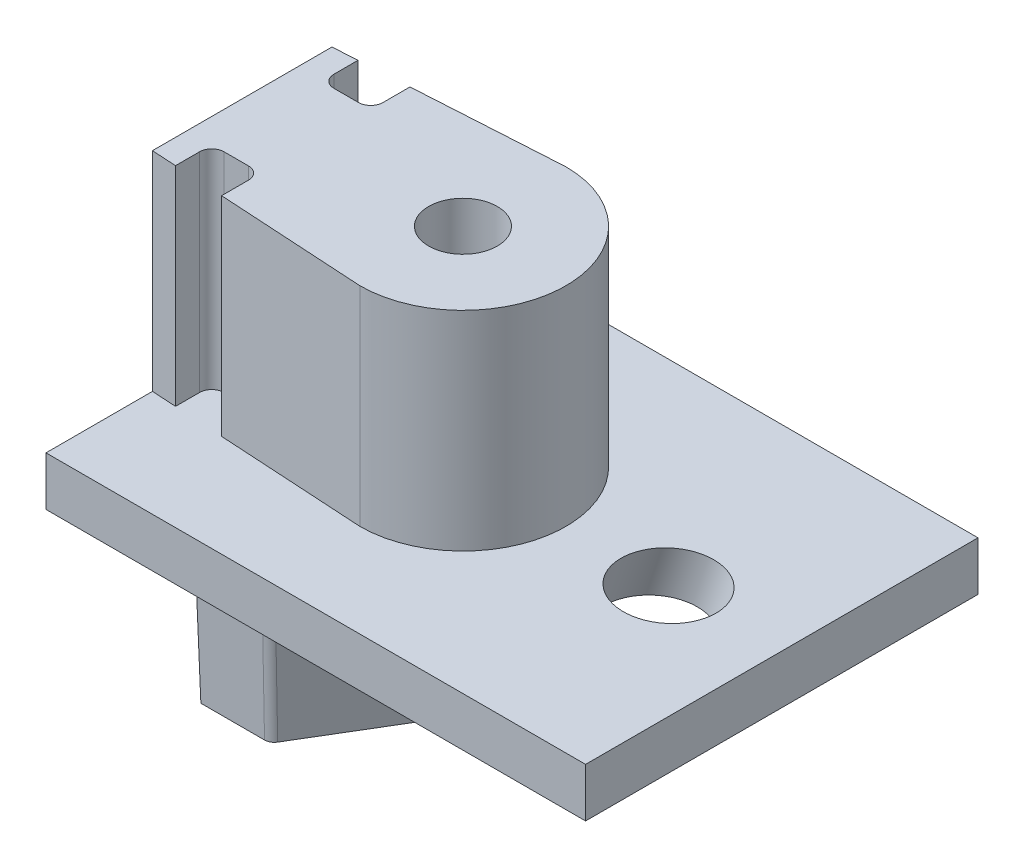
SolidWorks part; units mm, degrees
ref_plane "Front Plane" through (0, 0, 0) normal (0, 0, 1) x (1, 0, 0)
ref_plane "Top Plane" through (0, 0, 0) normal (0, 1, 0) x (1, 0, 0)
ref_plane "Right Plane" through (0, 0, 0) normal (1, 0, 0) x (0, 0, -1)
sketch "Sketch3" plane through (0, 0, 0) normal (0, 1, 0) x (1, 0, 0)
  line L0 (-5, 0.75) -> (0, 1.05) construction
  line L3 (0, -1.05) -> (-5, -0.75) construction
  line L4 (-2.5, 0.9) -> (-2, 0.93)
  line L6 (-4.25, 0) -> (-5.75, 0) construction
  line L7 (-2, 0.93) -> (-2, 0.56)
  line L8 (-2.5, 0.9) -> (-5, 0.9) construction
  line L9 (-2.5, 0.9) -> (-2.5, -0.9)
  line L10 (-2.5, -0.9) -> (-5, -0.9) construction
  line L11 (-5, 0.9) -> (-5, -0.9) construction
  line L12 (-2, 0.96) -> (-1.5, 0.96) construction
  line L13 (-2, 0.96) -> (-2, 0.56) construction
  line L14 (-2, 0.56) -> (-1.5, 0.56)
  line L15 (-1.5, 0.96) -> (-1.5, 0.56)
  line L16 (-1.5, -0.56) -> (-2, -0.56)
  line L17 (-1.5, -0.56) -> (-1.5, -0.96)
  line L18 (-1.5, -0.96) -> (-2, -0.96) construction
  line L19 (-2, -0.56) -> (-2, -0.96) construction
  line L21 (-2.5, -0.9) -> (-2, -0.93)
  line L22 (-2, -0.93) -> (-2, -0.56)
  line L23 (-1.5, 0.96) -> (0, 1.05)
  line L24 (0, -1.05) -> (-1.5, -0.96)
  circle A2 centre (0, 0) radius 0.6 construction
  circle A3 centre (0, 0) radius 0.4 construction
  circle A4 centre (-5, 0) radius 0.35 construction
  circle A5 centre (0, 0) radius 1.05 construction
  circle A6 centre (-5, 0) radius 0.75 construction
  arc A7 (-5, 0.9) -> (-5, -0.9) centre (-5, 0) ccw construction
  arc A8 (0, 1.05) -> (0, -1.05) centre (0, 0) cw
  point P4 (-2, -0.93)
  point P15 (-5, 0)
  point P16 (-2, 0.93)
  point P22 (-5, 0)
  dimension "D2" = 1.2
  dimension "D3" = 0.8
  dimension "D4" = 0.7
  dimension "D6" = 5
  dimension "D1" = 1.5
  dimension "D5" = 2.1
  dimension "D7" = 0.4
  dimension "D9" = 2.5
  dimension "D10" = 1.8
  dimension "D11" = 2.5
  dimension "D12" = 0.5
  dimension "D14" = 1.5
extrude "Boss-Extrude1" add sketch "Sketch3" along normal blind 2.125 contours L21 L22 L16 L17 L24 A8 L23 L15 L14 L7 L4 L9
sketch "Sketch4" plane through (0, 2.125, 0) normal (0, 1, 0) x (1, 0, 0)
  circle A0 centre (0, 0) radius 0.35
  point P9 (0, 0)
  dimension "D1" = 0.7
extrude "Through Holes" cut sketch "Sketch4" against normal through all
fillet "Fillet1" radius 0.125 4 edges at (-2, 1.0625, 0.56) (-1.5, 1.0625, 0.56) (-1.5, 1.0625, -0.56) (-2, 1.0625, -0.56)
sketch "Sketch5" plane through (0, 0, 0) normal (0, 1, 0) x (1, 0, 0)
  line L0 (-2.25, 0) -> (1.75, 0) construction
  line L1 (-2.25, -2) -> (1.75, -2)
  line L2 (-2.25, -2) -> (-2.25, 2)
  line L3 (-2.25, 2) -> (1.75, 2)
  line L4 (1.75, -2) -> (1.75, 2) construction
  line L5 (-2.25, -2) -> (1.75, 2) construction
  line L6 (-2.25, 2) -> (1.75, -2) construction
  line L8 (1.75, 2) -> (3.25, 2)
  line L9 (3.25, 2) -> (3.25, -2)
  line L10 (3.25, -2) -> (1.75, -2)
  circle A1 centre (0, 0) radius 0.125
  point P1 (-0.25, 0)
  dimension "D2" = 0.25
  dimension "D1" = 1.75
  dimension "D3" = 4
  dimension "D4" = 1.5
  dimension "D5" = 4
extrude "Boss-Extrude2" add sketch "Sketch5" against normal blind 0.5
sketch "Sketch6" plane through (0, 0, 0) normal (0, 0, 1) x (1, 0, 0)
  line L0 (3.25, 0) -> (3.25, 1.25)
  line L1 (3.25, 1.25) -> (1.75, 1.75)
  line L2 (1.75, 1.75) -> (1.75, 0)
  line L3 (1.75, 0) -> (3.25, 0)
  line L4 (2.5, 1.5) -> (1.6412, -1.0764)
  dimension "D1" = 1.25
  dimension "D2" = 1.75
ref_plane "Plane1" through (0.7, 2.1, 0) normal (0.3162, 0.9487, 0) x (0.9487, -0.3162, 0)
sketch "Sketch8" plane through (0.7, 2.1, 0) normal (0.3162, 0.9487, 0) x (0.9487, -0.3162, 0)
  line L0 (2.6879, 0) -> (1.1068, 0) construction
  line L2 (2.6879, 0) -> (1.9879, 0) construction
  circle A0 centre (1.9879, 0) radius 0.46
  dimension "D1" = 0.92
  dimension "D2" = 0.7
extrude "Cut-Extrude1" cut sketch "Sketch8" against normal through all
sketch "Sketch9" plane through (0, 0, 0) normal (0, -1, 0) x (1, 0, 0)
  line L0 (-2.25, 2) -> (-2.25, -2)
  line L1 (-2.25, -2) -> (-3.715, -2)
  line L2 (-3.715, -2) -> (-3.715, 2)
  line L3 (-3.715, 2) -> (-2.25, 2)
extrude "Cut-Extrude2" cut sketch "Sketch9" against normal through all both and the other way through all
sketch "Sketch10" plane through (0, -0.5, 0) normal (0, -1, 0) x (1, 0, 0)
  line L0 (-1.5, 1.25) -> (-1.5, -1.25)
  line L1 (-1.5, -1.25) -> (-0.75, -1.25)
  line L2 (-0.75, -1.25) -> (0, 0)
  line L3 (-2.25, 0) -> (1.75, 0) construction
  line L4 (0, 0) -> (-0.75, 1.25)
  line L5 (-0.75, 1.25) -> (-1.5, 1.25)
  line L6 (0, 0) -> (-1.5, 0) construction
  point P8 (-1.5, 0)
  dimension "D1" = 1.5
  dimension "D2" = 2.5
  dimension "D3" = 0.75
  dimension "D4" = 0.75
extrude "Boss-Extrude3" add sketch "Sketch10" along normal blind 1.75
chamfer "Chamfer1" distance 1.8 angle 2.5 4 edges at (-1.125, -2.25, -1.25) (-0.375, -2.25, -0.625) (-0.375, -2.25, 0.625) (-1.125, -2.25, 1.25) first distance on face at (-1.125, -1.375, -1.25) first distance on face at (-0.3129, -1.2, -0.5214) first distance on face at (-0.3129, -1.2, 0.5214) first distance on face at (-1.125, -1.375, 1.25)
fillet "Fillet2" radius 0.1 2 edges at (-0.7729, -1.375, 1.2096) (-0.7729, -1.375, -1.2096)
